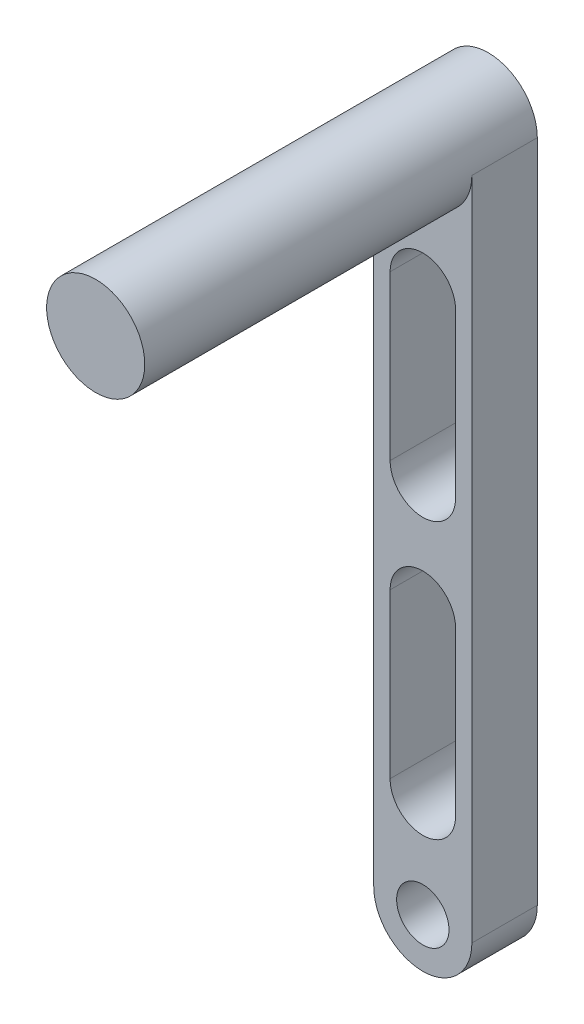
SolidWorks part; units mm, degrees
material "PEI"
ref_plane "Front Plane" through (0, 0, 0) normal (0, 0, 1) x (1, 0, 0)
ref_plane "Top Plane" through (0, 0, 0) normal (0, 1, 0) x (1, 0, 0)
ref_plane "Right Plane" through (0, 0, 0) normal (1, 0, 0) x (0, 0, -1)
sketch "Sketch1" plane through (0, 0, 0) normal (0, 0, 1) x (1, 0, 0)
  line L0 (0, -50.8) -> (0, 50.8) construction
  line L1 (-7.5, -50.8) -> (-7.5, 50.8)
  line L2 (7.5, -50.8) -> (7.5, 50.8)
  line L3 (0, -35.3) -> (0, -10.3) construction
  line L4 (-5, -35.3) -> (-5, -10.3)
  line L5 (5, -35.3) -> (5, -10.3)
  line L6 (0, 31.8) -> (0, 6.8) construction
  line L7 (5, 31.8) -> (5, 6.8)
  line L8 (-5, 31.8) -> (-5, 6.8)
  line L9 (-5, 19.3) -> (5, 19.3) construction
  line L10 (-5, -22.8) -> (5, -22.8) construction
  line L12 (0, 58.3) -> (0, 36.8) construction
  arc A0 (-7.5, -50.8) -> (7.5, -50.8) centre (0, -50.8) ccw
  arc A1 (7.5, 50.8) -> (-7.5, 50.8) centre (0, 50.8) ccw
  circle A2 centre (0, -50.8) radius 4
  arc A4 (-5, -35.3) -> (5, -35.3) centre (0, -35.3) ccw
  arc A5 (5, -10.3) -> (-5, -10.3) centre (0, -10.3) ccw
  arc A6 (5, 31.8) -> (-5, 31.8) centre (0, 31.8) ccw
  arc A7 (-5, 6.8) -> (5, 6.8) centre (0, 6.8) ccw
  circle A8 centre (0, 50.8) radius 7.5
  point P2 (0, 0)
  point P14 (0, -22.8)
  point P19 (0, 19.3)
  point P30 (0, -5.3)
  point P32 (0, -46.8)
  point P33 (0, -40.3)
  point P35 (0, 1.8)
  point P37 (0, 43.3)
  dimension "D3" = 8
  dimension "D1" = 101.6
  dimension "D2" = 15
  dimension "D4" = 10
  dimension "D5" = 6.5
  dimension "20" = 25
  dimension "D6" = 6.5
extrude "Boss-Extrude1" add sketch "Sketch1" along normal blind 10 contours A8 L1 A0 L2 A7 L8 A6 L7 A5 L5 A4 L4 A2 region at (-6.3987, 0, 0)
extrude "Boss-Extrude2" add sketch "Sketch1<4>" along normal blind 60 contours A1 A8 region at (0, 50.8, 0)
sketch "Sketch1<4>" plane through (0, 0, 0) normal (0, 0, 1) x (1, 0, 0) same geometry as "Sketch1"
sketch "Sketch2" plane through (0, 0, 60) normal (0, 0, 1) x (1, 0, 0)
  point P0 (0, 50.8)
